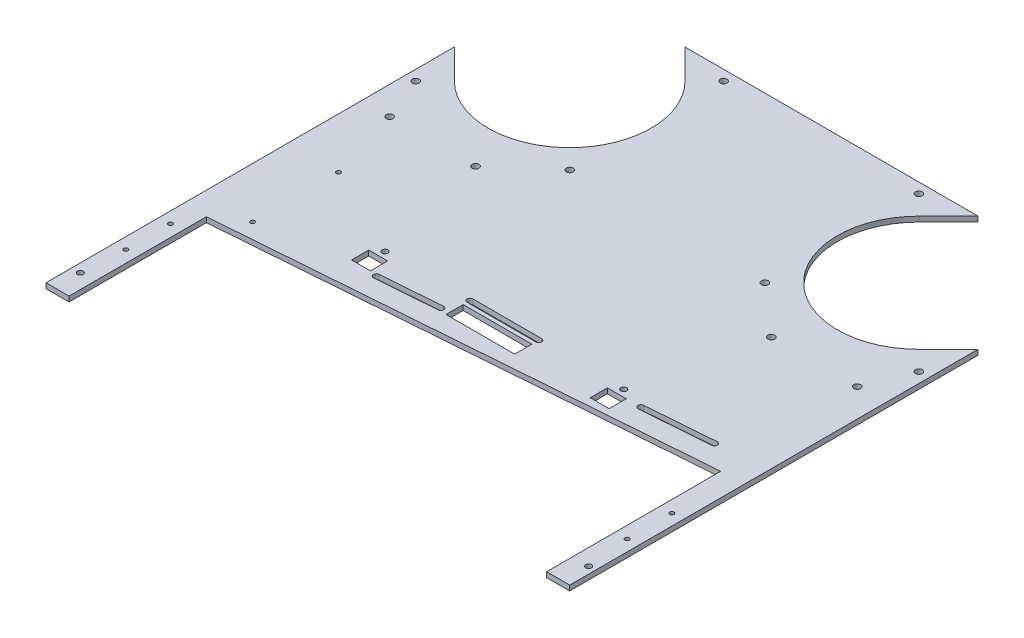
SolidWorks part; units mm, degrees
material "6061 Alloy"
ref_plane "Front Plane" through (0, 0, 0) normal (0, 0, 1) x (1, 0, 0)
ref_plane "Top Plane" through (0, 0, 0) normal (0, 1, 0) x (1, 0, 0)
ref_plane "Right Plane" through (0, 0, 0) normal (1, 0, 0) x (0, 0, -1)
sketch "Sketch1" plane through (0, 0, 0) normal (0, 1, 0) x (1, 0, 0)
  line L0 (0, 0) -> (0, 200)
  line L1 (0, 200) -> (305, 200)
  line L2 (305, 200) -> (305, 35.3098)
  line L3 (291.5711, -3.6044) -> (13.4289, -25)
  line L4 (0, 0) -> (0, -105)
  line L5 (0, -105) -> (13.4289, -105)
  line L6 (13.4289, -105) -> (13.4289, -25)
  line L7 (305, 35.3098) -> (305, -105)
  line L8 (305, -105) -> (291.5711, -105)
  line L9 (291.5711, -105) -> (291.5711, -3.6044)
  dimension "D1" = 305
  dimension "D2" = 85.601
  dimension "D3" = 200
  dimension "D4" = 13.4289
  dimension "D5" = 13.4289
  dimension "D6" = 105
  dimension "D7" = 305
  dimension "D8" = 80
sheet metal parameters "Sheet-Metal1" thickness 3 parameters "D1"=0.7366
base flange "Base-Flange1" sketch "Sketch1" thickness 3 reverse thickness direction no parameters "D1"=0.7366
hole_wizard "M3 Tapped Hole1" positions "Sketch6" profile "Sketch5" tap size "M3" standard "ISO"
sketch "Sketch6" plane through (0, 0, 0) normal (0, 1, 0) x (1, 0, 0)
  line L0 (0, 200) -> (0, -105) construction
  line L1 (305, -105) -> (305, 200) construction
  line L2 (0, -105) -> (13.4289, -105) construction
  line L3 (291.5711, -105) -> (305, -105) construction
  point P0 (6.5, -39)
  point P2 (6.5, -65)
  point P4 (298.5, -39)
  point P6 (298.5, -65)
  dimension "D1" = 6.5
  dimension "D3" = 6.5
  dimension "D5" = 26
  dimension "D6" = 26
  dimension "D7" = 40
  dimension "D8" = 40
sketch "Sketch5" plane through (6.5, 0, 39) normal (1, 0, 0) x (0, 0, 1)
  line L0 (0, 0) -> (0, 8.2511)
  line L1 (0, 8.2511) -> (1.25, 7.5)
  line L2 (1.25, 7.5) -> (1.25, 0)
  line L5 (1.25, 0) -> (0, 0)
  line L10 (0, 8.2511) -> (-1.25, 7.5) construction
  line L11 (0, -6.35) -> (0, 107.95) construction
  dimension "Tap Drill Dia." = 2.5
  dimension "Tap Drill Depth" = 7.5
  dimension "Drill Angle" = 118
cosmetic thread "Hole Thread1" parameters "D1"=3, "D2"=3
cosmetic thread "Hole Thread2" parameters "D1"=3, "D2"=3
cosmetic thread "Hole Thread3" parameters "D1"=3, "D2"=3
cosmetic thread "Hole Thread4" parameters "D1"=3, "D2"=3
sketch "Sketch11" plane through (0, 0, 0) normal (0, 1, 0) x (1, 0, 0)
  line L0 (0, 132.8249) -> (17.2124, 115.6124)
  line L1 (0, 200) -> (0, -105) construction
  line L2 (17.2124, 115.6124) -> (0, 115.6124) construction
  line L3 (84.3876, 182.7876) -> (67.1751, 200)
  line L4 (305, 200) -> (0, 200) construction
  line L5 (220.6124, 182.7876) -> (237.8249, 200)
  line L6 (287.7876, 115.6124) -> (305, 132.8249)
  line L7 (305, -105) -> (305, 200) construction
  line L8 (287.7876, 115.6124) -> (305, 115.6124) construction
  line L9 (0, 132.8249) -> (0, 200)
  line L10 (0, 200) -> (67.1751, 200)
  circle A0 centre (50.8, 149.2) radius 47.5
  circle A1 centre (254.2, 149.2) radius 47.5
  circle A2 centre (95.6437, 194.0437) radius 1.9844
  circle A3 centre (5.9563, 104.3563) radius 1.9844
  circle A4 centre (95.6437, 104.3563) radius 1.9844
  circle A5 centre (209.3563, 104.3563) radius 1.9844
  circle A6 centre (299.0437, 104.3563) radius 1.9844
  circle A7 centre (209.3563, 194.0437) radius 1.9844
  circle A8 centre (66.3384, 78.8315) radius 2
  circle A9 centre (16.3384, 78.8315) radius 2
  circle A10 centre (288.6616, 78.8319) radius 2
  circle A11 centre (238.6616, 78.8319) radius 2
  line M10 (0, 200) -> (0, -105)
  line M16 (305, -105) -> (305, 200)
  line M17 (305, 200) -> (0, 200)
  dimension "D2" = 95
  dimension "D3" = 95
  dimension "D8" = 3.9688
  dimension "D9" = 3.9688
  dimension "D11" = 3.9688
  dimension "D15" = 3.9687
  dimension "D16" = 3.9687
  dimension "D19" = 3.9687
  dimension "D18" = 4
  dimension "D20" = 4
  dimension "D21" = 4
  dimension "D22" = 4
  dimension "D1" = 45
  dimension "D4" = 45
  dimension "D5" = 5.9563
  dimension "D6" = 89.6874
  dimension "D7" = 95.6437
  dimension "D10" = 5.9563
  dimension "D12" = 5.9563
  dimension "D13" = 95.6437
  dimension "D14" = 95.6437
  dimension "D17" = 5.9563
extrude "Cut-Extrude1" cut sketch "Sketch11" against normal through all contours A0 L3 L0 M17 M10 | A0 | A1 | A1 L6 L5 M16 M17 | A2 | A3 | A4 | A7 | A5 | A6 | A9 | A8 | A11 | A10 region at (1.1934, 0, -166.4124) region at (271.4124, 0, -198.8066) region at (50.8, 0, -149.2) region at (254.2, 0, -149.2) region at (95.6437, 0, -194.0437) region at (5.9563, 0, -104.3563) region at (95.6437, 0, -104.3563) region at (209.3563, 0, -104.3563) region at (299.0437, 0, -104.3563) region at (209.3563, 0, -194.0437) region at (66.3384, 0, -78.8315) region at (16.3384, 0, -78.8315) region at (288.6616, 0, -78.8319) region at (238.6616, 0, -78.8319) normal cut yes
hole_wizard "M3 Tapped Hole3" positions "Sketch13" profile "Sketch12" tap size "M3" standard "ISO"
sketch "Sketch13" plane through (0, 0, 0) normal (0, 1, 0) x (1, 0, 0)
  point P0 (29.4743, 35.8573)
  point P3 (29.4743, -14.1427)
sketch "Sketch12" plane through (29.4743, 0, -35.8573) normal (1, 0, 0) x (0, 0, 1)
  line L0 (0, 0) -> (0, 8.2511)
  line L1 (0, 8.2511) -> (1.25, 7.5)
  line L2 (1.25, 7.5) -> (1.25, 0)
  line L5 (1.25, 0) -> (0, 0)
  line L10 (0, 8.2511) -> (-1.25, 7.5) construction
  line L11 (0, -6.35) -> (0, 107.95) construction
  dimension "Tap Drill Dia." = 2.5
  dimension "Tap Drill Depth" = 7.5
  dimension "Drill Angle" = 118
cosmetic thread "Hole Thread7" parameters "D1"=3, "D2"=3
cosmetic thread "Hole Thread8" parameters "D1"=3, "D2"=3
sketch "Sketch14" plane through (0, 0, 0) normal (0, 1, 0) x (1, 0, 0)
  line L0 (152.5, 200) -> (152.5, -163.8054) construction
  line L1 (237.8249, 200) -> (67.1751, 200) construction
  line L3 (77.5, -4.533) -> (227.5, -4.533)
  line L4 (77.5, -4.533) -> (77.5, 5.467)
  line L5 (77.5, 5.467) -> (227.5, 5.467)
  line L6 (227.5, -4.533) -> (227.5, 5.467)
  line L11 (77.5, -4.533) -> (227.5, 5.467) construction
  line L12 (77.5, 5.467) -> (227.5, -4.533) construction
  line L13 (88.5, 5.467) -> (88.5, -4.533)
  line L14 (216.5, 5.467) -> (216.5, -4.533)
  line L15 (132.5, 5.467) -> (132.5, -4.533)
  line L16 (172.5, 5.467) -> (172.5, -4.533)
  line L21 (13.4289, -25) -> (291.5711, -3.6044) construction
  line L22 (227.5, -4.533) -> (227.5, -8.533) construction
  point P4 (152.5, 0.467)
  dimension "D1" = 150
  dimension "D2" = 10
  dimension "D3" = 11
  dimension "D4" = 11
  dimension "D5" = 20
  dimension "D6" = 20
  dimension "D7" = 4
extrude "QRD Slots" cut sketch "Sketch14" against normal blind 10 contours L5 L14 L3 L6 | L16 L5 L15 L3 | L13 L5 L4 L3 region at (83, 0, -0.467) region at (152.5, 0, -0.467) region at (222, 0, -0.467) normal cut yes
sketch "Sketch15" plane through (0, 0, 0) normal (0, 1, 0) x (1, 0, 0)
  line L0 (275.8299, 8.5925) -> (92.848, -5.483) construction
  line L1 (275.9603, 6.8975) -> (92.9784, -7.178)
  line L2 (275.6995, 10.2875) -> (92.7176, -3.788)
  arc A0 (275.9603, 6.8975) -> (275.6995, 10.2875) centre (275.8299, 8.5925) ccw
  arc A1 (92.7176, -3.788) -> (92.9784, -7.178) centre (92.848, -5.483) ccw
  arc A2 (235.8173, 7.2196) -> (236.0781, 3.8296) centre (235.9477, 5.5246) ccw
  arc A5 (127.8753, -4.4937) -> (127.6145, -1.1037) centre (127.7449, -2.7987) ccw
  point P3 (184.339, 1.5547)
  dimension "D1" = 1.7
  dimension "D2" = 35
  dimension "D3" = 40
extrude "Wall Mounting Slots" cut sketch "Sketch15" against normal blind 10 contours L1 A5 L2 A1 | A2 L1 A0 L2 region at (255.8888, 0, -7.0586) region at (110.2965, 0, 4.1409) normal cut yes
hole_wizard "M3 Clearance Hole1" positions "Sketch17" profile "Sketch18" hole size "M3" standard "ISO"
sketch "Sketch17" plane through (0, 0, 0) normal (0, 1, 0) x (1, 0, 0)
  line L0 (77.5, 5.467) -> (88.5, 5.467) construction
  line L1 (216.5, 5.467) -> (227.5, 5.467) construction
  line L2 (222, 5.467) -> (222, 9.467) construction
  line L4 (83, 9.467) -> (83, 5.467) construction
  point P0 (83, 9.467)
  point P3 (222, 9.467)
  dimension "D1" = 4
  dimension "D2" = 4
sketch "Sketch18" plane through (83, 0, -9.467) normal (1, 0, 0) x (0, 0, 1)
  line L0 (0, 0) -> (0, 11.0215)
  line L1 (0, 11.0215) -> (1.7, 10)
  line L2 (1.7, 10) -> (1.7, 0)
  line L5 (1.7, 0) -> (0, 0)
  line L10 (0, 11.0215) -> (-1.7, 10) construction
  line L11 (0, -6.35) -> (0, 107.95) construction
  dimension "Hole Dia." = 3.4
  dimension "Hole Depth" = 10
  dimension "Drill Angle" = 118
sketch "Sketch19" plane through (0, 0, 0) normal (0, 1, 0) x (1, 0, 0)
  line L0 (132.5, 9.467) -> (172.5, 9.467) construction
  line L1 (132.5, 11.167) -> (172.5, 11.167)
  line L2 (132.5, 7.767) -> (172.5, 7.767)
  line L3 (132.5, 5.467) -> (172.5, 5.467) construction
  line L5 (132.5, 9.467) -> (132.5, 5.467) construction
  line L6 (172.5, 9.467) -> (172.5, 5.467) construction
  line L7 (132.5, 5.467) -> (132.5, -4.533) construction
  line L8 (172.5, 5.467) -> (172.5, -4.533) construction
  arc A0 (132.5, 11.167) -> (132.5, 7.767) centre (132.5, 9.467) ccw
  arc A1 (172.5, 7.767) -> (172.5, 11.167) centre (172.5, 9.467) ccw
  point P2 (152.5, 9.467)
  dimension "D1" = 1.7
  dimension "D2" = 4
extrude "Cut-Extrude2" cut sketch "Sketch19" against normal through all normal cut yes
sketch "Sketch20" plane through (0, 0, 0) normal (0, 1, 0) x (1, 0, 0)
  line L1 (0, 132.8249) -> (0, -105) construction
  line L2 (0, -105) -> (13.4289, -105) construction
  line L3 (305, -105) -> (305, 132.8249) construction
  line L4 (291.5711, -105) -> (305, -105) construction
  circle A0 centre (301, -90) radius 1.7
  circle A1 centre (5, -90) radius 1.7
  dimension "D3" = 3.4
  dimension "D6" = 3.4
  dimension "D1" = 5
  dimension "D2" = 15
  dimension "D4" = 4
  dimension "D5" = 15
extrude "Cut-Extrude3" cut sketch "Sketch20" against normal through all normal cut yes
flat pattern "Flat-Pattern1" [suppressed]
sketch "Bend-Lines1" plane through (0, 0, 0) normal (0, 1, 0) x (1, 0, 0)
sketch3d "Bounding-Box1" [suppressed]
  line L0 (-304.8, 200, 0) -> (0, 200, 0) construction
  line L1 (-304.8, 0, 0) -> (0, 0, 0) construction
  line L2 (-304.8, 200, 0) -> (-304.8, 0, 0) construction
  line L3 (0, 200, 0) -> (0, 0, 0) construction
equation "\"D5@Sketch1\"=\"D4@Sketch1\""
equation "\"D6@Sketch14\"=\"D5@Sketch14\""
